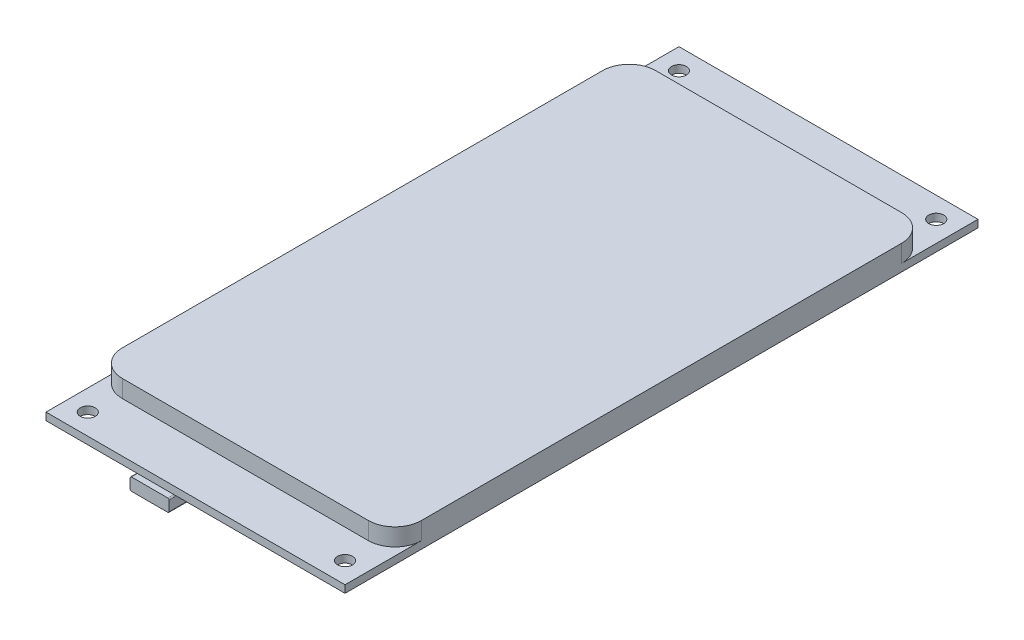
SolidWorks part; units mm, degrees
note: The reader was unsure of these and kept them because the rebuilt part matched: shared geometry of "Sketch4<2>", "Sketch6<3>", "Sketch5<2>".
ref_plane "Front Plane" through (0, 0, 0) normal (0, 0, 1) x (1, 0, 0)
ref_plane "Top Plane" through (0, 0, 0) normal (0, 1, 0) x (1, 0, 0)
ref_plane "Right Plane" through (0, 0, 0) normal (1, 0, 0) x (0, 0, -1)
sketch "Sketch1" plane through (0, 0, 0) normal (0, 1, 0) x (1, 0, 0)
  line L1 (0, 0) -> (60, 0)
  line L2 (0, 0) -> (0, 127)
  line L3 (0, 127) -> (60, 127)
  line L4 (60, 0) -> (60, 127)
  dimension "D1" = 60
  dimension "D2" = 127
extrude "Boss-Extrude1" add sketch "Sketch1" along normal blind 1.5
sketch "Sketch2" plane through (0, 1.5, 0) normal (0, 1, 0) x (1, 0, 0)
  line L0 (60, 127) -> (0, 127) construction
  line L1 (0, 127) -> (0, 0) construction
  line L2 (60, 0) -> (60, 127) construction
  line L3 (0, 0) -> (60, 0) construction
  circle A0 centre (4.19, 122.81) radius 1.5
  circle A1 centre (55.81, 122.81) radius 1.5
  circle A2 centre (4.19, 4.19) radius 1.5
  circle A3 centre (55.81, 4.19) radius 1.5
  dimension "D1" = 4.19
  dimension "D3" = 4.19
  dimension "D2" = 4.19
  dimension "D4" = 4.19
  dimension "D5" = 4.19
  dimension "D6" = 4.19
  dimension "D7" = 4.19
  dimension "D8" = 4.19
extrude "Cut-Extrude1" cut sketch "Sketch2" against normal up to next
sketch "Sketch3" plane through (0, 1.5, 0) normal (0, 1, 0) x (1, 0, 0)
  line L0 (0, 127) -> (0, 0) construction
  line L1 (5.3247, 117) -> (54.6753, 117)
  line L2 (0, 111.6753) -> (0, 15.3247)
  line L3 (5.3247, 10) -> (54.6753, 10)
  line L4 (60, 111.6753) -> (60, 15.3247)
  line L5 (60, 0) -> (60, 127) construction
  line L6 (60, 127) -> (0, 127) construction
  line L7 (0, 0) -> (60, 0) construction
  arc A0 (0, 15.3247) -> (5.3247, 10) centre (5.3247, 15.3247) ccw
  arc A1 (54.6753, 10) -> (60, 15.3247) centre (54.6753, 15.3247) ccw
  arc A2 (60, 111.6753) -> (54.6753, 117) centre (54.6753, 111.6753) ccw
  arc A3 (0, 111.6753) -> (5.3247, 117) centre (5.3247, 111.6753) cw
  point P14 (0, 10)
  point P17 (60, 10)
  point P22 (0, 117)
  dimension "D4" = 5.3247
  dimension "D1" = 107
  dimension "D2" = 10
  dimension "D3" = 10
extrude "Boss-Extrude2" add sketch "Sketch3" along normal blind 3.5
sketch "Sketch4" plane through (0, 0, 0) normal (0, 0, 1) x (1, 0, 0)
  line L0 (0, 0) -> (60, 0) construction
  line L1 (18.35, 0) -> (25.65, 0)
  line L2 (18.1, -0.25) -> (18.1, -2.25)
  line L3 (18.35, -2.5) -> (25.65, -2.5)
  line L4 (25.9, -0.25) -> (25.9, -2.25)
  line L5 (0, 1.5) -> (0, 0) construction
  arc A0 (18.35, 0) -> (18.1, -0.25) centre (18.35, -0.25) ccw
  arc A1 (18.1, -2.25) -> (18.35, -2.5) centre (18.35, -2.25) ccw
  arc A2 (25.65, -2.5) -> (25.9, -2.25) centre (25.65, -2.25) ccw
  arc A3 (25.65, 0) -> (25.9, -0.25) centre (25.65, -0.25) cw
  point P8 (18.1, 0)
  point P11 (18.1, -2.5)
  point P14 (25.9, -2.5)
  point P17 (25.9, 0)
  dimension "D3" = 0.25
  dimension "D1" = 7.8
  dimension "D2" = 2.5
  dimension "D4" = 18.1
extrude "Boss-Extrude3" add sketch "Sketch4" against normal blind 4.8 separate body
extrude "Boss-Extrude4" add sketch "Sketch4<2>" along normal blind 1.2
sketch "Sketch4<2>" plane through (0, 0, 0) normal (0, 0, 1) x (1, 0, 0) same geometry as "Sketch4"
sketch "Sketch5" plane through (0, 0, 0) normal (-1, 0, 0) x (0, 0, 1)
  line L0 (-127, 0) -> (0, 0) construction
  line L1 (-28.1, 0) -> (-42.5, 0)
  line L2 (-28.1, 0) -> (-28.1, -2)
  line L3 (-28.1, -2) -> (-42.5, -2)
  line L4 (-42.5, 0) -> (-42.5, -2)
  line L5 (0, 1.5) -> (0, 0) construction
  dimension "D1" = 14.4
  dimension "D2" = 2
  dimension "D3" = 42.5
extrude "Boss-Extrude5" add sketch "Sketch5" against normal blind 14.5
sketch "Sketch6" plane through (0, 0, -127) normal (0, 0, -1) x (-1, 0, 0)
  line L1 (-34.2, 0) -> (-28.3087, 0)
  line L2 (-35, -2.15) -> (-35, -3.55)
  line L3 (-34.75, -3.8) -> (-27.75, -3.8)
  line L4 (-27.5, -2.15) -> (-27.5, -3.55)
  line L5 (-60, 1.5) -> (-60, 0) construction
  line L6 (-34.75, -1.9) -> (-34.7, -1.9)
  line L7 (-27.8087, -1.9) -> (-27.75, -1.9)
  line L11 (-34.45, -1.65) -> (-34.45, -0.25)
  line L12 (-34.2, 0) -> (-28.3087, 0)
  line L13 (-34.45, -0.25) -> (-34.45, -1.9)
  line L15 (-28.0587, -0.25) -> (-28.0587, -1.65)
  arc A0 (-28.3087, 0) -> (-28.0587, -0.25) centre (-28.3087, -0.25) cw
  arc A1 (-28.0587, -1.65) -> (-27.8087, -1.9) centre (-27.8087, -1.65) ccw
  arc A2 (-27.75, -1.9) -> (-27.5, -2.15) centre (-27.75, -2.15) cw
  arc A3 (-27.5, -3.55) -> (-27.75, -3.8) centre (-27.75, -3.55) cw
  arc A4 (-34.75, -3.8) -> (-35, -3.55) centre (-34.75, -3.55) cw
  arc A5 (-35, -2.15) -> (-34.75, -1.9) centre (-34.75, -2.15) cw
  arc A6 (-34.7, -1.9) -> (-34.45, -1.65) centre (-34.7, -1.65) ccw
  arc A7 (-34.45, -0.25) -> (-34.2, 0) centre (-34.2, -0.25) cw
  point P12 (-28.0587, -1.9)
  point P20 (-27.5, -3.8)
  point P23 (-35, -3.8)
  dimension "D2" = 0.25
  dimension "D1" = 7.5
  dimension "D3" = 32.5
  dimension "D4" = 0.55
extrude "Boss-Extrude6" add sketch "Sketch6" along normal blind 1.4 separate body
extrude "Boss-Extrude7" add sketch "Sketch6<3>" against normal blind 7.6
sketch "Sketch6<3>" plane through (0, 0, -127) normal (0, 0, -1) x (-1, 0, 0) same geometry as "Sketch6"
sketch "Sketch7" plane through (0, 0, 0) normal (-1, 0, 0) x (0, 0, 1)
  line L0 (-127, 0) -> (-42.5, 0) construction
  line L1 (-105.9, 0) -> (-99.5, 0)
  line L2 (-105.9, 0) -> (-105.9, -5.3)
  line L3 (-105.9, -5.3) -> (-99.5, -5.3)
  line L4 (-99.5, 0) -> (-99.5, -5.3)
  line L6 (-127, 1.5) -> (-127, 0) construction
  dimension "D1" = 6.4
  dimension "D2" = 5.3
  dimension "D3" = 27.5
extrude "Boss-Extrude8" add sketch "Sketch7" against normal blind 15
sketch "Sketch8" plane through (0, 0, 0) normal (-1, 0, 0) x (0, 0, 1)
  circle A0 centre (-102.7, -2.65) radius 2.45
extrude "Boss-Extrude9" add sketch "Sketch8" along normal blind 1
extrude "Boss-Extrude10" add sketch "Sketch5<2>" along normal blind 0.25
sketch "Sketch5<2>" plane through (0, 0, 0) normal (-1, 0, 0) x (0, 0, 1) same geometry as "Sketch5"
sketch "Sketch9" plane through (0, 0, -127) normal (0, 0, -1) x (-1, 0, 0)
  line L0 (-28.3087, 0) -> (0, 0) construction
  line L1 (-21.8, 0) -> (-16, 0)
  line L2 (-21.8, 0) -> (-21.8, -12)
  line L3 (-21.8, -12) -> (-16, -12)
  line L4 (-16, 0) -> (-16, -12)
  line L5 (0, 1.5) -> (0, 0) construction
  dimension "D1" = 12
  dimension "D2" = 5.8
  dimension "D3" = 16
extrude "Boss-Extrude11" add sketch "Sketch9" against normal blind 5.8
